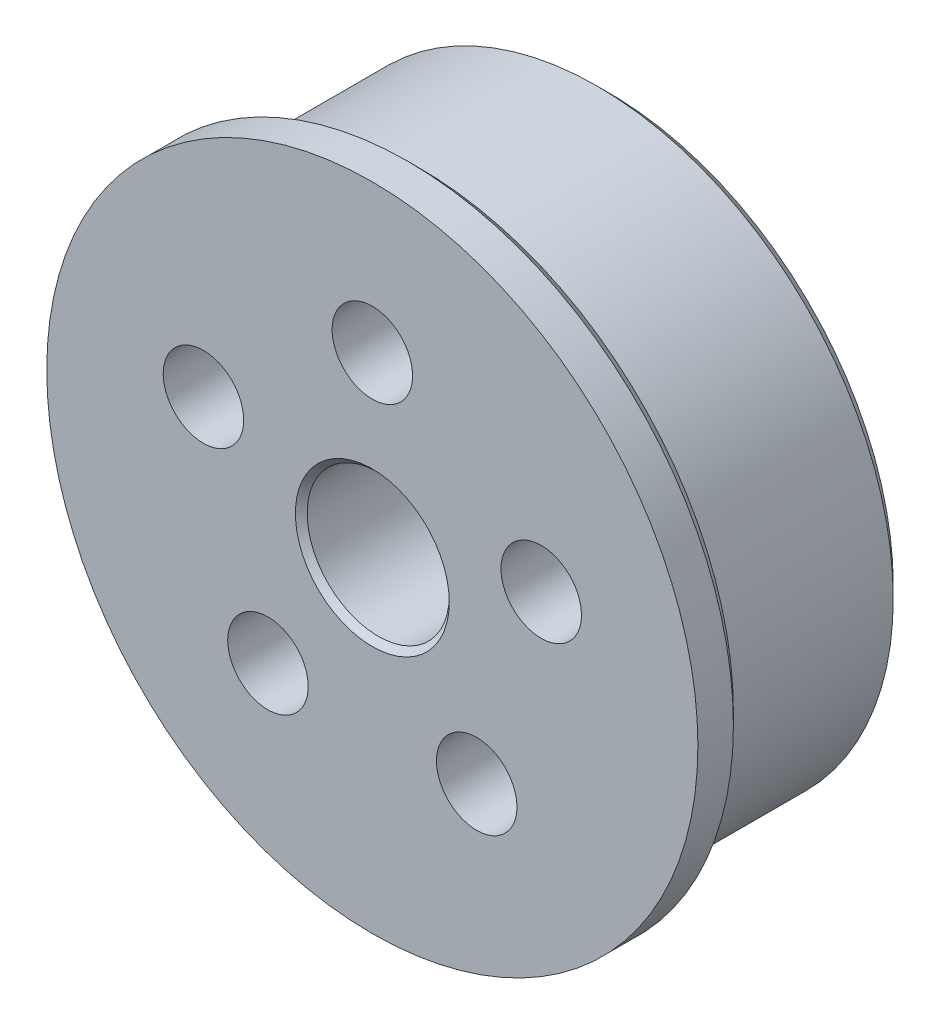
SolidWorks part; units mm, degrees
material "A2017"
ref_plane "正面" through (0, 0, 0) normal (0, 0, 1) x (1, 0, 0)
ref_plane "平面" through (0, 0, 0) normal (0, 1, 0) x (1, 0, 0)
ref_plane "右側面" through (0, 0, 0) normal (1, 0, 0) x (0, 0, -1)
sketch "ｽｹｯﾁ1" plane through (0, 0, 0) normal (0, 0, 1) x (1, 0, 0)
  circle A0 centre (0, 0) radius 12.5
  circle A1 centre (0, 7.5) radius 1.5
  circle A2 centre (0, 0) radius 7.5 construction
  circle A3 centre (7.1329, 2.3176) radius 1.5
  circle A4 centre (4.4084, -6.0676) radius 1.5
  circle A5 centre (-4.4084, -6.0676) radius 1.5
  circle A6 centre (-7.1329, 2.3176) radius 1.5
  point P16 (0, 0)
  dimension "D1" = 25
  dimension "D2" = 15
  dimension "D3" = 3
  dimension "D4" = 5
extrude "ﾎﾞｽ - 押し出し1" add sketch "ｽｹｯﾁ1" along normal blind 10
sketch "ｽｹｯﾁ3" plane through (0, 0, 10) normal (0, 0, 1) x (1, 0, 0)
  circle A0 centre (0, 0) radius 13.75
  circle A2 centre (0, 0) radius 12.5
  circle A3 centre (0, 0) radius 12.5
  dimension "D1" = 0
  dimension "D2" = 27.5
extrude "ﾎﾞｽ - 押し出し3" add sketch "ｽｹｯﾁ3" against normal blind 2
sketch "ｽｹｯﾁ4" plane through (0, 0, 0) normal (0, 0, -1) x (-1, 0, 0)
  circle A0 centre (0, 0) radius 3
  dimension "D1" = 6
extrude "ｶｯﾄ - 押し出し1" cut sketch "ｽｹｯﾁ4" against normal through all
hole_wizard "M3 穴付きねじ用座ぐり穴1" positions "ｽｹｯﾁ5" profile "ｽｹｯﾁ6" counterbore size "M3" standard "JIS" end condition through all
sketch "ｽｹｯﾁ5" plane through (0, 0, 0) normal (0, 0, -1) x (-1, 0, 0)
  point P0 (0, 7.5)
  point P3 (7.1329, 2.3176)
  point P6 (4.4084, -6.0676)
  point P9 (-4.4084, -6.0676)
  point P12 (-7.1329, 2.3176)
sketch "ｽｹｯﾁ6" plane through (0, 7.5, 0) normal (1, 0, 0) x (0, 1, 0)
  line L0 (0, 0) -> (0, 10)
  line L1 (0, 10) -> (1.7, 10)
  line L3 (1.7, 10) -> (1.7, 4)
  line L4 (1.7, 4) -> (3.5, 4)
  line L5 (3.5, 4) -> (3.5, 0)
  line L7 (3.5, 0) -> (0, 0)
  line L11 (0, -6.35) -> (0, 107.95) construction
  dimension "通し穴の直径" = 3.4
  dimension "通し穴の深さ" = 10
  dimension "座ぐり穴の直径" = 7
  dimension "座ぐり穴の深さ" = 4
chamfer "面取り1" distance 0.5 angle 45 2 edges at (12.5, 0, 0) (13.75, 0, 8)
chamfer "面取り2" distance 0.25 angle 45 7 edges at (-3, 0, 0) (-3, 0, 10) (0.9084, -6.0676, 0) (-7.9084, -6.0676, 0) (-10.6329, 2.3176, 0) (-3.5, 7.5, 0) (3.6329, 2.3176, 0)
